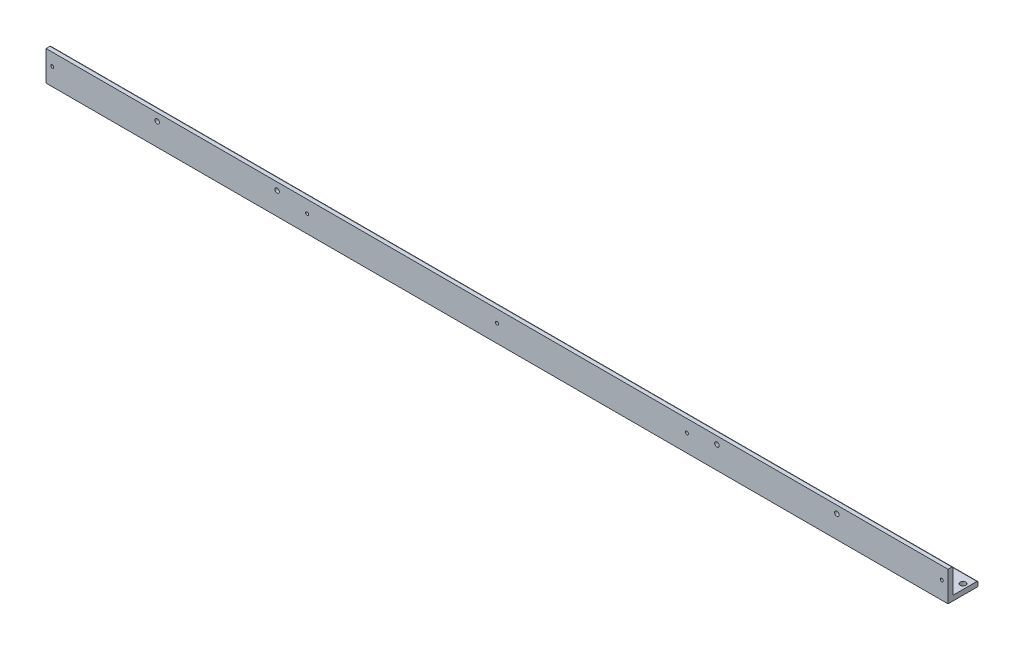
SolidWorks part; units mm, degrees
material "ALUMINUM 6061"
ref_plane "Front" through (0, 0, 0) normal (0, 0, 1) x (1, 0, 0)
ref_plane "Top" through (0, 0, 0) normal (0, 1, 0) x (1, 0, 0)
ref_plane "Right" through (0, 0, 0) normal (1, 0, 0) x (0, 0, -1)
ref_axis "Axis1" through (0, 50, 0) along (0, -1, 0)
sketch "Sketch1" plane through (0, 0, 0) normal (1, 0, 0) x (0, 0, -1)
  line L0 (0, 38.1) -> (0, 0)
  line L1 (0, 0) -> (38.1, 0)
  line L2 (38.1, 0) -> (38.1, 4.826)
  line L3 (36.576, 6.35) -> (6.35, 6.35)
  line L4 (6.35, 6.35) -> (6.35, 36.576)
  line L5 (4.826, 38.1) -> (0, 38.1)
  arc A0 (6.35, 36.576) -> (4.826, 38.1) centre (4.826, 36.576) ccw
  arc A1 (38.1, 4.826) -> (36.576, 6.35) centre (36.576, 4.826) ccw
  point P9 (6.35, 38.1)
  point P12 (38.1, 6.35)
  dimension "D5" = 1.524
  dimension "D1" = 38.1
  dimension "D2" = 38.1
  dimension "D3" = 6.35
  dimension "D4" = 6.35
extrude "Extrude1" add sketch "Sketch1" along normal mid plane 1146.175
hole_wizard "1/4 Clearance Hole1" positions "Sketch3" profile "Sketch2" hole size "1/4" standard "Ansi Inch" end condition through all
sketch "Sketch3" plane through (0, 6.35, 0) normal (0, 1, 0) x (-1, 0, 0)
  line L0 (-573.0875, -36.576) -> (-573.0875, -6.35) construction
  line L1 (-573.0875, 0) -> (573.0875, 0) construction
  line L2 (573.0875, -36.576) -> (573.0875, -6.35) construction
  point P0 (-566.7375, -25.4)
  point P5 (566.7375, -25.4)
  dimension "D1" = 6.35
  dimension "D4" = 6.35
  dimension "D5" = 25.4
sketch "Sketch2" plane through (566.7375, 6.35, -25.4) normal (1, 0, 0) x (0, 0, 1)
  line L0 (0, 0) -> (0, 6.35)
  line L1 (0, 6.35) -> (3.5712, 6.35)
  line L2 (3.5712, 6.35) -> (3.5712, 0)
  line L5 (3.5712, 0) -> (0, 0)
  line L11 (0, -6.35) -> (0, 107.95) construction
  dimension "Thru Hole Dia." = 7.1425
  dimension "Thru Hole Depth" = 6.35
hole_wizard "#10-24 Tapped Hole1" positions "Sketch5" profile "Sketch4" tap size "#10-24" standard "ANSI Inch" end condition up to next
sketch "Sketch5" plane through (0, 0, 0) normal (0, 0, 1) x (1, 0, 0)
  line L1 (573.0875, 0) -> (-573.0875, 0) construction
  line L3 (0, 38.1) -> (0, 0) construction
  line L4 (573.0875, 38.1) -> (-573.0875, 38.1) construction
  point P1 (-565.15, 22.225)
  point P9 (565.15, 22.225)
  point P35 (-241.3, 22.225)
  point P46 (241.3, 22.225)
  point P53 (0, 22.225)
  dimension "D1" = 565.15
  dimension "D2" = 241.3
  dimension "D3" = 565.15
  dimension "D4" = 22.225
  dimension "D5" = 241.3
sketch "Sketch4" plane through (-565.15, 22.225, 0) normal (1, 0, 0) x (0, -1, 0)
  line L0 (0, 0) -> (0, 6.35)
  line L1 (0, 6.35) -> (1.8986, 6.35)
  line L2 (1.8986, 6.35) -> (1.8986, 0)
  line L5 (1.8986, 0) -> (0, 0)
  line L11 (0, -6.35) -> (0, 107.95) construction
  dimension "Thru Tap Drill Dia." = 3.7973
  dimension "Thru Tap Drill Depth" = 6.35
cosmetic thread "Hole Thread1"
cosmetic thread "Hole Thread5"
cosmetic thread "Hole Thread6"
cosmetic thread "Hole Thread7"
cosmetic thread "Hole Thread8"
hole_wizard "#10 Clearance Hole1" positions "Sketch7" profile "Sketch6" hole size "#10" standard "ANSI Inch" end condition up to next
sketch "Sketch7" plane through (0, 0, 0) normal (0, 0, 1) x (1, 0, 0)
  line L0 (573.0875, 38.1) -> (-573.0875, 38.1) construction
  point P0 (-431.8, 28.575)
  point P2 (-279.4, 28.575)
  point P4 (279.4, 28.575)
  point P6 (431.8, 28.575)
  dimension "D1" = 152.4
  dimension "D2" = 279.4
  dimension "D3" = 279.4
  dimension "D4" = 152.4
  dimension "D5" = 9.525
sketch "Sketch6" plane through (-431.8, 28.575, 0) normal (1, 0, 0) x (0, -1, 0)
  line L0 (0, 0) -> (0, 6.35)
  line L1 (0, 6.35) -> (2.8067, 6.35)
  line L2 (2.8067, 6.35) -> (2.8067, 0)
  line L5 (2.8067, 0) -> (0, 0)
  line L11 (0, -6.35) -> (0, 107.95) construction
  dimension "Thru Hole Dia." = 5.6134
  dimension "Thru Hole Depth" = 6.35
